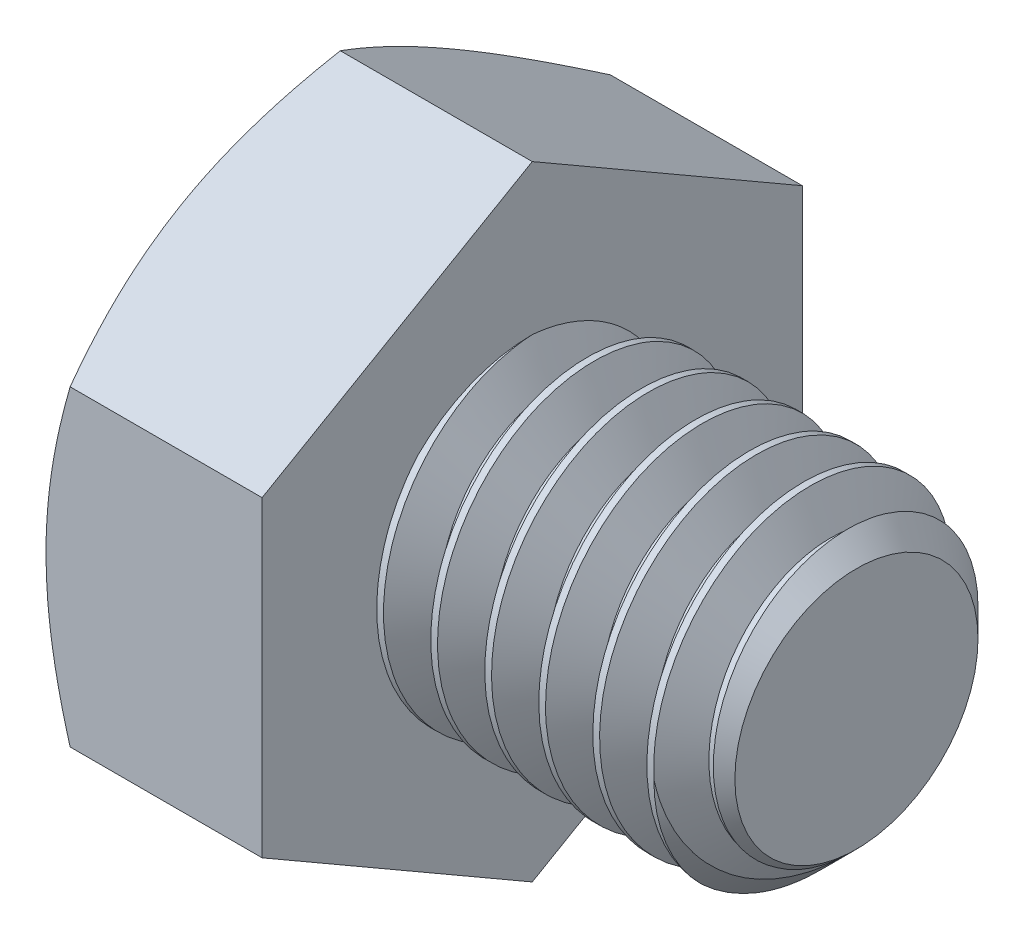
SolidWorks part; units mm, degrees
ref_plane "Front Plane" through (0, 0, 0) normal (0, 0, 1) x (1, 0, 0)
ref_plane "Top Plane" through (0, 0, 0) normal (0, 1, 0) x (1, 0, 0)
ref_plane "Right Plane" through (0, 0, 0) normal (1, 0, 0) x (0, 0, -1)
sketch "Sketch1" plane through (0, 0, 0) normal (0, 0, 1) x (1, 0, 0)
  line L0 (-5, 0) -> (5, 0) construction
  line L1 (-1, 5) -> (-1, -5) construction
  line L2 (-5, 5) -> (-5, -5) construction
  line L3 (5, 3) -> (5, -3) construction
  point P8 (1.5, -3)
  dimension "Thread Dia" = 6
  dimension "Hex" = 10
  dimension "Head Ht" = 4
  dimension "Length" = 6
  dimension "D1" = 3.5
ref_plane "Plane2" through (5, 0, 0) normal (1, 0, 0) x (0, 0, -1)
sketch "Sketch2" plane through (5, 0, 0) normal (1, 0, 0) x (0, 0, -1)
  circle A0 centre (0, 0) radius 3
extrude "Boss-Extrude1" add sketch "Sketch2" against normal up to vertex (6 mm away) up to point (-1, -5, 0)
sketch "Sketch4" plane through (5, 0, 0) normal (1, 0, 0) x (0, 0, -1)
  circle A1 centre (0, 0) radius 3
  circle A2 centre (0, 0) radius 3
  dimension "D1" = 0
curve "Helix/Spiral1" pitch 1 height 7 turns 7 parameters "Pitch"=1
chamfer "Chamfer1" distance 0.75 angle 45 1 edges at (5, 0, -3)
sketch "Sketch5" plane through (0, 0, 0) normal (0, 0, 1) x (1, 0, 0)
  line L0 (5, 3) -> (5.375, 2.3505)
  line L1 (5.375, 2.3505) -> (5.5, 2.3505)
  line L2 (5.5, 2.3505) -> (5.875, 3)
  line L3 (5, 3) -> (5.875, 3)
  line L4 (5.4375, 2.3505) -> (5.4375, 3) construction
  line L5 (5.1875, 2.6752) -> (5.6875, 2.6752) construction
  line L6 (5, -3) -> (5, 3) construction
  dimension "D1" = 60
  dimension "D2" = 0.125
  dimension "D3" = 0.5
sweep "Cut-Sweep1" cut profiles "Sketch5" path "Helix/Spiral1" align with end faces yes
sketch "Sketch3" plane through (-1, 0, 0) normal (-1, 0, 0) x (0, 0, 1)
  line L0 (0, 5) -> (0, -5) construction
  line L1 (-5, -2.8868) -> (0, -5.7735)
  line L2 (0, -5.7735) -> (5, -2.8868)
  line L3 (5, -2.8868) -> (5, 2.8868)
  line L4 (5, 2.8868) -> (0, 5.7735)
  line L5 (0, 5.7735) -> (-5, 2.8868)
  line L6 (-5, 2.8868) -> (-5, -2.8868)
  circle A0 centre (0, 0) radius 5 construction
extrude "Boss-Extrude2" add sketch "Sketch3" along normal up to vertex (4 mm away) up to point (-5, -5, 0)
sketch "Sketch6" plane through (-5, 0, 0) normal (-1, 0, 0) x (0, 0, 1)
  circle A0 centre (0, 0) radius 5 construction
  circle A1 centre (0, 0) radius 5
extrude "Cut-Extrude1" cut sketch "Sketch6" against normal through all draft 60 flip side to cut
sketch "Sketch9" plane through (0, 0, 0) normal (0, 0, 1) x (1, 0, 0)
  line L0 (-1, 3) -> (-1, 0)
  line L1 (-1, 0) -> (-46, 0)
  line L2 (-46, 0) -> (-49, 3)
  line L3 (-49, 3) -> (-1, 3)
  line L4 (-5, 0) -> (5, 0) construction
  line L5 (-1, 5) -> (-1, -5) construction
  line L6 (5, 3) -> (5, -3) construction
  dimension "D1" = 45
  dimension "MinThreadLg" = 54
revolve "Revolve1" [suppressed] add sketch "Sketch9" angle 360 about L1
equation "\"D2@Sketch5\" = \"Pitch@Helix/Spiral1\"*.125"
equation "\"D3@Sketch5\" = \"Pitch@Helix/Spiral1\"*.50"
equation "\"D3@Helix/Spiral1\" = \"Length@Sketch1\"+\"Pitch@Helix/Spiral1\""
equation "\"D1@Chamfer1\" = \"Pitch@Helix/Spiral1\"*.750"
equation "\"D1@Sketch1\" = \"Pitch@Helix/Spiral1\"*3.50"
